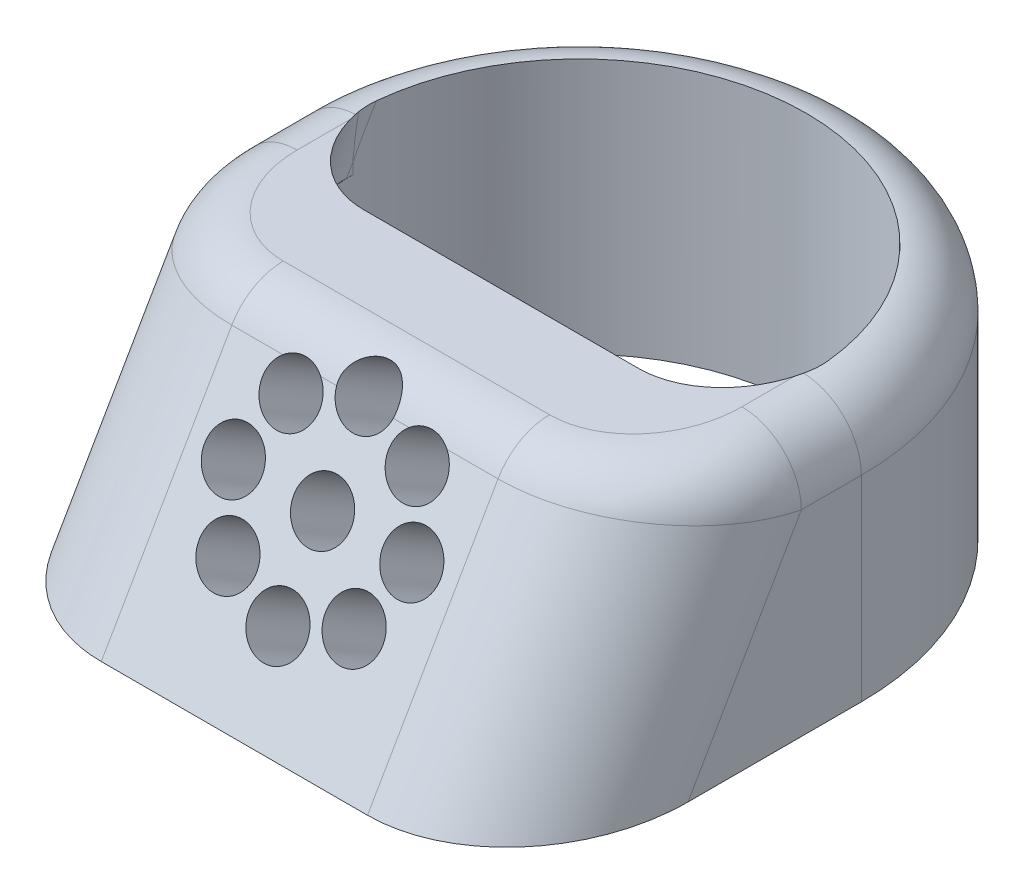
SolidWorks part; units mm, degrees
ref_plane "Front Plane" through (0, 0, 0) normal (0, 0, 1) x (1, 0, 0)
ref_plane "Top Plane" through (0, 0, 0) normal (0, 1, 0) x (1, 0, 0)
ref_plane "Right Plane" through (0, 0, 0) normal (1, 0, 0) x (0, 0, -1)
sketch "Sketch1" plane through (0, 0, 0) normal (0, 1, 0) x (1, 0, 0)
  line L0 (-47.375, 0) -> (-47.375, -22)
  line L2 (47.375, -22) -> (47.375, 0)
  line L3 (-38.1, 0) -> (-38.1, -22)
  line L5 (38.1, -22) -> (38.1, 0)
  line L6 (-47.375, -22) -> (-38.1, -22)
  line L7 (38.1, -22) -> (47.375, -22)
  arc A0 (38.1, 0) -> (-38.1, 0) centre (0, 0) ccw
  arc A1 (47.375, 0) -> (-47.375, 0) centre (0, 0) ccw
  dimension "D1" = 76.2
  dimension "D2" = 47.375
  dimension "D3" = 22
extrude "Boss-Extrude1" add sketch "Sketch1" along normal blind 43
extrude "Boss-Extrude2" add sketch "Sketch1<2>" along normal blind 6.35 contours L5 A0 L3 | L2 A1 L0 A0 L5 L3 region at (0, 0, -46.2007)
sketch "Sketch1<2>" plane through (0, 0, 0) normal (0, 1, 0) x (1, 0, 0) same geometry as "Sketch1"
sketch "Sketch8" plane through (0, 0, 0) normal (1, 0, 0) x (0, 0, -1)
  line L0 (-58, 0) -> (-33.1739, 43)
  line L3 (-38, 0) -> (-58, 0)
  line L4 (-38, 0) -> (-13.1739, 43)
  line L5 (-13.1739, 43) -> (-33.1739, 43)
  line L6 (-22, 43) -> (0, 43) construction
  dimension "D1" = 20
  dimension "D2" = 60
  dimension "D3" = 38
extrude "Boss-Extrude3" add sketch "Sketch8" against normal up to surface and the other way up to surface up to face at (-47.375, 21.5, 11) other way up to face at (47.375, 21.5, 11)
sketch "Sketch9" plane through (0, 16.4545, 28.5) normal (0, -0.5, -0.866) x (1, 0, 0)
  circle A0 centre (0, 6) radius 15
  dimension "D1" = 30
  dimension "D2" = 6
extrude "Cut-Extrude4" [suppressed] cut sketch "Sketch9" against normal through all
sketch "Sketch10" plane through (47.375, 0, 0) normal (1, 0, 0) x (0, 0, -1)
  line L0 (-38, 0) -> (-22, 0)
  line L1 (-22, 0) -> (-22, 27.7128)
  line L2 (-22, 27.7128) -> (-38, 0)
extrude "Boss-Extrude4" add sketch "Sketch10" against normal up to surface (9.275 mm away) up to face at (38.1, 22.7426, 11.4348)
sketch "Sketch11" plane through (-47.375, 0, 0) normal (-1, 0, 0) x (0, 0, 1)
  line L0 (22, 0) -> (38, 0)
  line L1 (38, 0) -> (22, 27.7128)
  line L2 (22, 27.7128) -> (22, 0)
extrude "Boss-Extrude5" add sketch "Sketch11" against normal up to surface (9.275 mm away) up to face at (-38.1, 22.7426, 11.4348)
sketch "Sketch12" plane through (0, 0, 0) normal (0, -1, 0) x (1, 0, 0)
  line L5 (-38.1, 0) -> (-38.1, 38)
  line L6 (-38.1, 38) -> (0, 38.1)
  line L10 (0, 38.1) -> (38.1, 38)
  line L11 (38.1, 38) -> (38.1, 0)
  arc A3 (38.1, 0) -> (-38.1, 0) centre (0, 0) ccw
  line M6 (-38.1, 0) -> (-38.1, 38)
  line M7 (-38.1, 38) -> (38.1, 38)
  line M8 (38.1, 38) -> (38.1, 0)
extrude "Boss-Extrude6" add sketch "Sketch12" against normal blind 34 contours A3 M8 M7 | A3 M7 M6 region at (-29.703, 0, 29.49) region at (29.703, 0, 29.49)
sketch "Sketch13" plane through (0, 25.1147, 43.5) normal (0, 0.5, 0.866) x (1, 0, 0)
  line L1 (-47.375, 20.6521) -> (47.375, 20.6521) construction
  line L2 (0, 15.6521) -> (0, -14.3479) construction
  circle A21 centre (0, 15.6521) radius 4.825
  circle A22 centre (0, -14.3479) radius 4.825
  circle A23 centre (10.6066, 11.2587) radius 4.825
  circle A24 centre (15, 0.6521) radius 4.825
  circle A25 centre (10.6066, -9.9545) radius 4.825
  circle A26 centre (0, -14.3479) radius 4.825
  circle A27 centre (-10.6066, -9.9545) radius 4.825
  circle A28 centre (-15, 0.6521) radius 4.825
  circle A29 centre (-10.6066, 11.2587) radius 4.825
  circle A36 centre (0, 0.6521) radius 4.825
  point P31 (0, 0.6521)
  point P41 (0, 0.6521)
  dimension "D1" = 9.65
  dimension "D2" = 5
  dimension "D3" = 30
  dimension "D4" = 8
extrude "Cut-Extrude6" cut sketch "Sketch13" against normal up to surface (17.3205 mm away) contours A21 | A23 | L2 | A29 | A24 | A25 | A28 | A26 | L2 | A22 | A27 | A36 region at (0, 38.6699, 35.6739) region at (0, 12.6891, 50.6739) region at (10.6066, 34.8651, 37.8706) region at (15, 25.6795, 43.1739) region at (10.6066, 16.4939, 48.4772) region at (-10.6066, 16.4939, 48.4772) region at (-15, 25.6795, 43.1739) region at (-10.6066, 34.8651, 37.8706) up to face at (0, 26.0657, 22.951)
fillet "Fillet8" radius 15 2 edges at (-38.1, 38.5, 15.772) (38.1, 38.5, 15.772)
fillet "Fillet9" radius 25 2 edges at (47.375, 21.5, 45.587) (-47.375, 21.5, 45.587)
sketch "Sketch14" plane through (0, 0, 0) normal (0, -1, 0) x (1, 0, 0)
  circle A0 centre (-42.0864, -4.195) radius 2.125
  circle A1 centre (0, -42.295) radius 2.125
  circle A2 centre (42.0864, -4.195) radius 2.125
  arc A5 (42.0864, -4.195) -> (42.0069, 4.9278) centre (0, 0) cw construction
  arc A6 (-2.7586, 38) -> (2.7586, 38) centre (0, 0) ccw construction
  dimension "D1" = 4.25
  dimension "D4" = 42.295
  dimension "D2" = 38.1
extrude "Cut-Extrude7" cut sketch "Sketch14" against normal blind 8
fillet "Fillet10" radius 10 2 edges
fillet "Fillet11" radius 10 5 edges at (47.375, 43, 2.1532) (40.0527, 43, 24.7188) (0, 43, 33.1739) (-40.0527, 43, 24.7188) (-47.375, 43, 2.1532)
